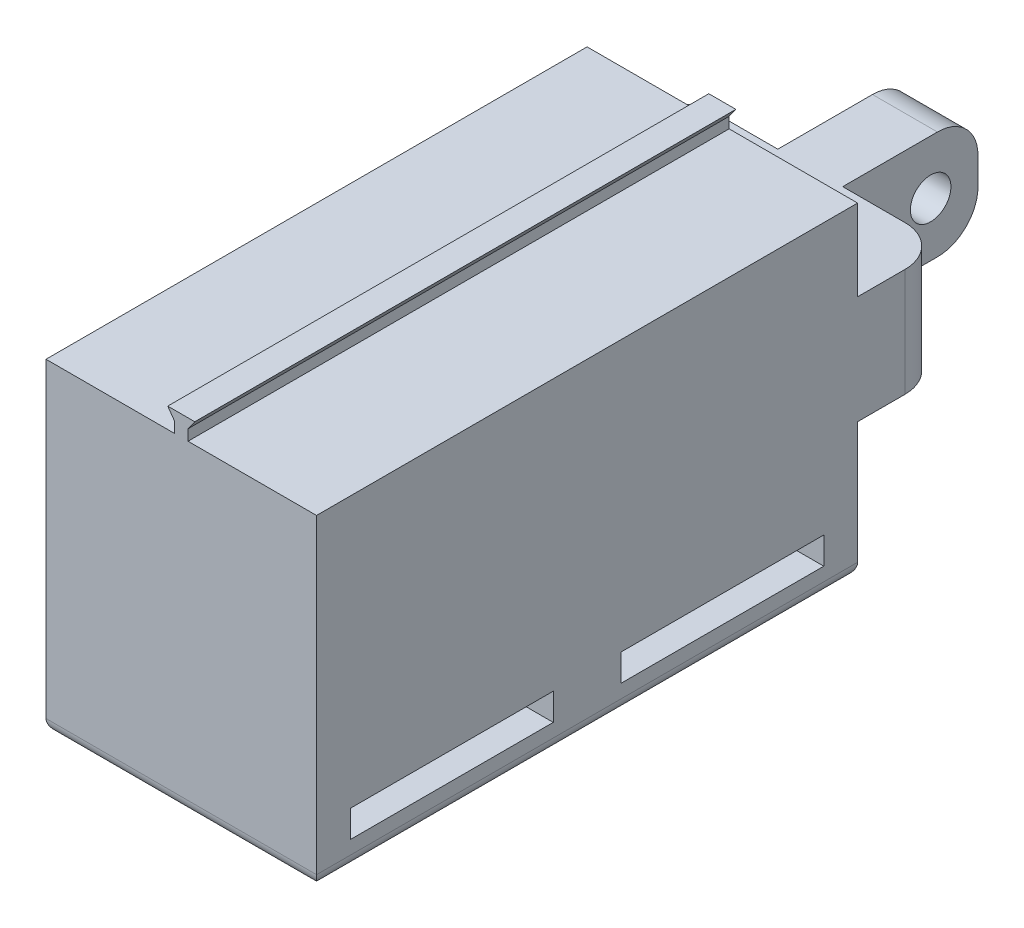
SolidWorks part; units mm, degrees
ref_plane "Alzado" through (0, 0, 0) normal (0, 0, 1) x (1, 0, 0)
ref_plane "Planta" through (0, 0, 0) normal (0, 1, 0) x (1, 0, 0)
ref_plane "Vista lateral" through (0, 0, 0) normal (1, 0, 0) x (0, 0, -1)
sketch "Croquis1" plane through (0, 0, 0) normal (1, 0, 0) x (0, 0, -1)
  line L0 (0, 9) -> (0, 1) construction
  line L9 (-1.5, 9) -> (-58, 9) construction
  line L18 (0, 9) -> (0, -9) construction
  line L19 (0, -9) -> (-58, -9) construction
  line L25 (0, 1) -> (-18, 1) construction
  line L26 (0, 1) -> (0, -2.6179) construction
  line L29 (0, -2.6179) -> (0, -9) construction
  line L31 (-1.5, 9) -> (-1.5, 1)
  line L32 (-18, 1) -> (-1.5, 1)
  line L35 (-58, -9) -> (-18, -9)
  line L56 (-58, 9) -> (-58, -9)
  line L59 (0, 9) -> (-58, 9) construction
  line L61 (-18, 1) -> (-18, -9)
  line L62 (-18, 9) -> (-18, 15)
  line L63 (-18, 15) -> (-58, 15)
  line L64 (-58, 15) -> (-58, 9)
  line L65 (-1.5, 9) -> (-18, 9)
  circle A0 centre (-5, 5) radius 1.5
  point P9 (0, 0)
  point P12 (0, 5)
  dimension "D6" = 3
  dimension "D1" = 58
  dimension "D2" = 10
  dimension "D3" = 40
  dimension "D4" = 8
  dimension "D5" = 6
  dimension "D7" = 5
  dimension "D8" = 3
extrude "Saliente-Extruir1" add sketch "Croquis1" along normal mid plane 20
sketch "Croquis2" plane through (0, 0, 0) normal (0, 1, 0) x (1, 0, 0)
  line L0 (-2.4, -11.5) -> (-10, -11.5)
  line L5 (10, -1.5) -> (-10, -1.5) construction
  line L6 (-10, -1.5) -> (-10, -18) construction
  line L7 (-10, -11.5) -> (-10, -1.5)
  line L8 (-2.4, -1.5) -> (2.4, -1.5) construction
  line L9 (-2.4, -1.5) -> (-2.4, -11.5)
  line L10 (-2.4, -11.5) -> (2.4, -11.5) construction
  line L11 (2.4, -1.5) -> (2.4, -11.5)
  line L12 (-10, -1.5) -> (-2.4, -1.5)
  line L13 (2.4, -11.5) -> (10, -11.5)
  line L14 (10, -1.5) -> (10, -18) construction
  line L15 (10, -11.5) -> (10, -1.5)
  line L16 (10, -1.5) -> (2.4, -1.5)
  point P6 (0, -1.5)
  dimension "D1" = 4.8
  dimension "D2" = 10
extrude "Cortar-Extruir1" cut sketch "Croquis2" against normal through all both and the other way through all
sketch "Croquis4" plane through (0, 0, 0) normal (1, 0, 0) x (0, 0, -1)
  line L0 (-58, -9) -> (-18, -9) construction
  line L1 (-55.5, -5) -> (-40.5, -5)
  line L2 (-55.5, -5) -> (-55.5, -7)
  line L3 (-55.5, -7) -> (-40.5, -7)
  line L4 (-40.5, -5) -> (-40.5, -7)
  line L5 (-55.5, -5) -> (-40.5, -7) construction
  line L6 (-55.5, -7) -> (-40.5, -5) construction
  line L7 (-18, -9) -> (-18, 1) construction
  line L8 (-35.5, -5) -> (-20.5, -5)
  line L9 (-35.5, -5) -> (-35.5, -7)
  line L10 (-35.5, -7) -> (-20.5, -7)
  line L11 (-20.5, -5) -> (-20.5, -7)
  line L12 (-58, 15) -> (-58, -9) construction
  point P0 (-48, -6)
  point P7 (-28, -7)
  point P16 (-48, -7)
  dimension "D1" = 2
  dimension "D2" = 2
  dimension "D3" = 15
  dimension "D4" = 10
  dimension "D5" = 10
extrude "Cortar-Extruir4" cut sketch "Croquis4" against normal through all both and the other way through all
fillet "Redondeo2" radius 1 4 edges at (10, -9, 38) (-10, -9, 38) (0, -9, 58) (0, -9, 18)
sketch "Croquis5" plane through (0, 0, 18) normal (0, 0, -1) x (-1, 0, 0)
  line L0 (-10, 15) -> (10, 15) construction
  line L1 (-0.5, 15) -> (0.5, 15)
  line L2 (-0.5, 15) -> (-0.5, 15.8)
  line L4 (0.5, 15) -> (0.5, 15.8)
  line L5 (-0.5, 15.8) -> (-1, 16.5)
  line L6 (-1, 16.5) -> (1, 16.5)
  line L7 (1, 16.5) -> (0.5, 15.8)
  point P6 (0, 15)
  point P8 (0, 16.5)
  dimension "D1" = 1
  dimension "D2" = 1.5
  dimension "D3" = 0.8
  dimension "D4" = 2
extrude "Saliente-Extruir2" add sketch "Croquis5" against normal up to surface (40 mm away) up to face at (0, 3.5, 58)
fillet "Redondeo3" radius 3 4 edges at (0, 9, 1.5) (0, 1, 1.5) (-10, 5, 11.5) (10, 5, 11.5)
